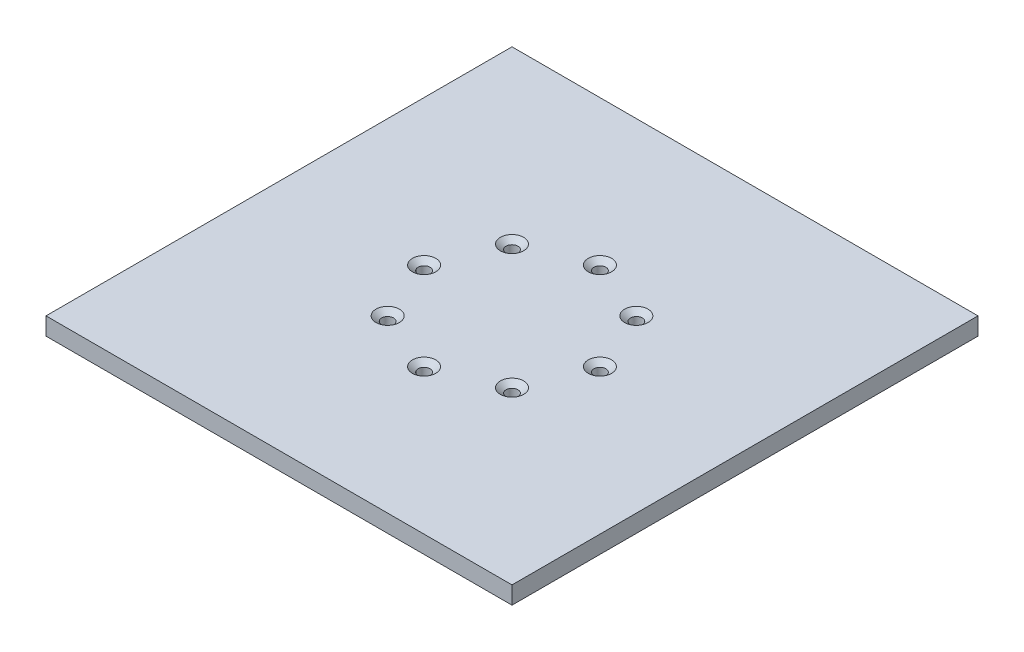
SolidWorks part; units mm, degrees
material "6061-T6 (SS)"
ref_plane "Front Plane" through (0, 0, 0) normal (0, 0, 1) x (1, 0, 0)
ref_plane "Top Plane" through (0, 0, 0) normal (0, 1, 0) x (1, 0, 0)
ref_plane "Right Plane" through (0, 0, 0) normal (1, 0, 0) x (0, 0, -1)
sketch "Sketch1" plane through (0, 0, 0) normal (0, 1, 0) x (1, 0, 0)
  line L1 (-84.1375, -84.1375) -> (84.1375, -84.1375)
  line L2 (-84.1375, -84.1375) -> (-84.1375, 84.1375)
  line L3 (-84.1375, 84.1375) -> (84.1375, 84.1375)
  line L4 (84.1375, -84.1375) -> (84.1375, 84.1375)
  line L10 (-84.1375, 84.1375) -> (0, 0) construction
  line L23 (0, 0) -> (84.1375, 84.1375) construction
  line L24 (0, 0) -> (-84.1375, -84.1375) construction
  line L25 (0, 0) -> (84.1375, -84.1375) construction
  circle A0 centre (0, 0) radius 38.1 construction
  circle A1 centre (0, 0) radius 41.275 construction
  point P0 (0, 0)
  point P1 (0, 0)
  point P2 (0, 0)
  point P3 (0, 0)
  point P27 (-84.1375, 0)
  dimension "D4" = 76.2
  dimension "D12" = 168.275
extrude "Boss-Extrude1" add sketch "Sketch1" along normal blind 6.35
ref_axis "Axis1" through (0, 0, 0) along (0, 1, 0)
hole_wizard "CSK for #8 Flat Head Machine Screw (100)1" positions "Sketch5" profile "Sketch4" countersink size "#8" standard "Ansi Inch" end condition through all
sketch "Sketch5" plane through (0, 6.35, 0) normal (0, 1, 0) x (-1, 0, 0)
  point P0 (0, 31.75)
  dimension "D1" = 31.75
sketch "Sketch4" plane through (0, 6.35, 31.75) normal (1, 0, 0) x (0, 0, 1)
  line L0 (0, 0) -> (0, 6.35)
  line L1 (0, 6.35) -> (2.1526, 6.35)
  line L2 (2.1526, 6.35) -> (2.1526, 1.7317)
  line L3 (2.1526, 1.7317) -> (4.2164, 0)
  line L5 (4.2164, 0) -> (0, 0)
  line L6 (-2.1526, 1.7317) -> (-4.2164, 0) construction
  line L11 (0, -6.35) -> (0, 107.95) construction
  dimension "Thru Hole Dia." = 4.3053
  dimension "Thru Hole Depth" = 6.35
  dimension "Near C'Sink Dia." = 8.4328
  dimension "Near C'Sink Angle" = 100
pattern_circular "CirPattern2" count 8 over 360 about axis through (0, 0, 0) along (0, 1, 0) of "CSK for #8 Flat Head Machine Screw (100)1"
